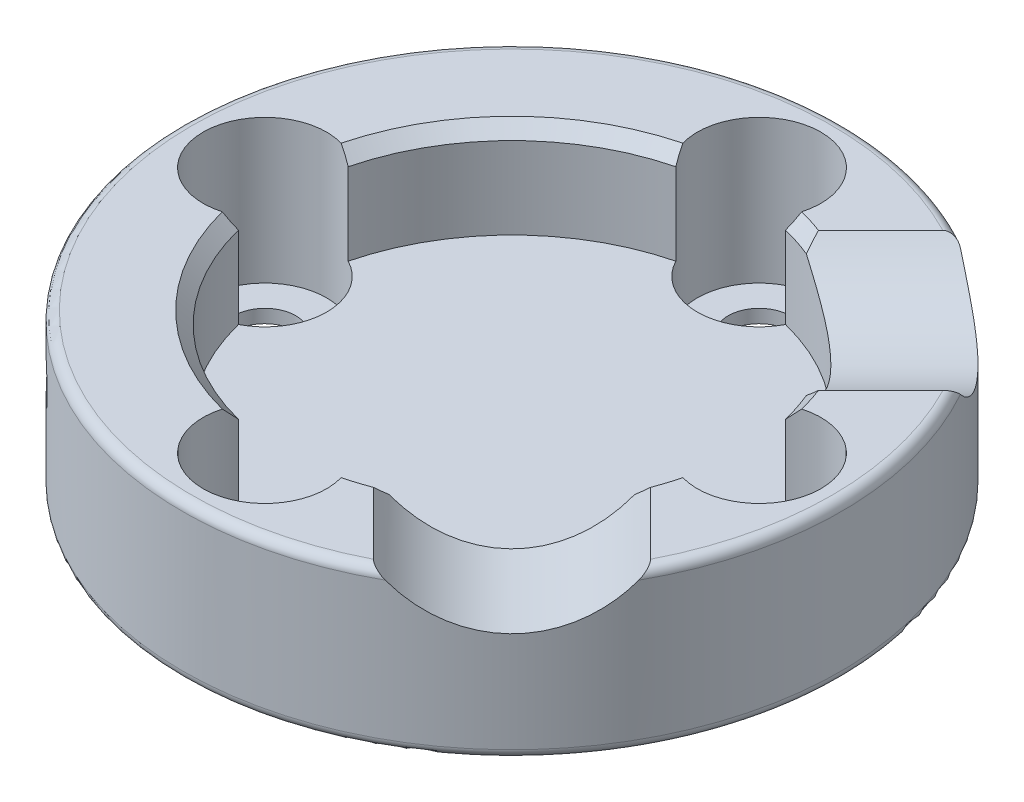
SolidWorks part; units mm, degrees
ref_plane "Front Plane" through (0, 0, 0) normal (0, 0, 1) x (1, 0, 0)
ref_plane "Top Plane" through (0, 0, 0) normal (0, 1, 0) x (1, 0, 0)
ref_plane "Right Plane" through (0, 0, 0) normal (1, 0, 0) x (0, 0, -1)
sketch "Sketch1" plane through (0, 0, 0) normal (0, 1, 0) x (1, 0, 0)
  circle A0 centre (0, 0) radius 26.67
  dimension "D1" = 53.34
extrude "Boss-Extrude1" add sketch "Sketch1" along normal blind 12.7 contours A0
sketch "Sketch2" plane through (0, 12.7, 0) normal (0, 1, 0) x (1, 0, 0)
  line L0 (0, 0) -> (0, 26.5974) construction
  line L1 (0, 0) -> (36.2469, 0) construction
  circle A0 centre (0, 20) radius 2.5
  circle A1 centre (20, 0) radius 2.5
  circle A2 centre (0, -20) radius 2.5
  circle A3 centre (-20, 0) radius 2.5
  point P15 (0, 0)
  dimension "D2" = 5
  dimension "D3" = 40
  dimension "D1" = 4
extrude "Cut-Extrude1" cut sketch "Sketch2" against normal blind 15.24
sketch "Sketch3" plane through (0, 12.7, 0) normal (0, 1, 0) x (1, 0, 0)
  circle A0 centre (0, 0) radius 18.25
  dimension "D1" = 36.5
extrude "Cut-Extrude2" cut sketch "Sketch3" against normal blind 7.62
sketch "Sketch4" plane through (0, 5.08, 0) normal (0, 1, 0) x (1, 0, 0)
  line L0 (0, 0) -> (42.5254, 0) construction
  line L1 (0, 0) -> (0, -15.78) construction
  circle A0 centre (0, 20) radius 5
  circle A1 centre (20, 0) radius 5
  circle A2 centre (0, -20) radius 5
  circle A3 centre (-20, 0) radius 5
  point P12 (0, 0)
  dimension "D1" = 10
  dimension "D2" = 4
extrude "Cut-Extrude3" cut sketch "Sketch4" against normal blind 4 and the other way through all
ref_axis "Axis1" through (0, 5.08, 0) along (0, 1, 0)
ref_plane "Plane1" through (0, 0, 0) normal (0.7071, 0, -0.7071) x (0, 1, 0)
sketch "Sketch5" plane through (0, 0, 0) normal (0.7071, 0, -0.7071) x (0, 1, 0)
  line L0 (0, 0) -> (25.4191, 0) construction
  line L1 (12.7, -26.67) -> (12.7, 26.67) construction
  circle A0 centre (8.128, 0) radius 1.905
  dimension "D1" = 3.81
  dimension "D2" = 4.572
extrude "Cut-Extrude4" cut sketch "Sketch5" against normal through all
fillet "Fillet1" radius 0.762 2 edges at (0, 0, 26.67) (0, 12.7, 26.67)
chamfer "Chamfer1" distance 1 angle 45 4 edges at (-12.9047, 12.7, -12.9047) (-12.9047, 12.7, 12.9047) (12.9047, 12.7, 12.9047) (12.9047, 12.7, -12.9047)
sketch "Sketch6" plane through (0, 0, 0) normal (0.7071, 0, -0.7071) x (0, 1, 0)
  line L0 (0, 0) -> (36.4067, 0) construction
  line L1 (5.08, 0) -> (12.7, 0) construction
  circle A0 centre (19.05, 0) radius 10.16
  dimension "D2" = 20.32
  dimension "D1" = 19.05
extrude "Cut-Extrude5" cut sketch "Sketch6" along normal blind 35.814
pattern_circular "CirPattern1" count 2 over 90 about axis through (0, 5.08, 0) along (0, 1, 0) of "Cut-Extrude5" reverse direction yes
